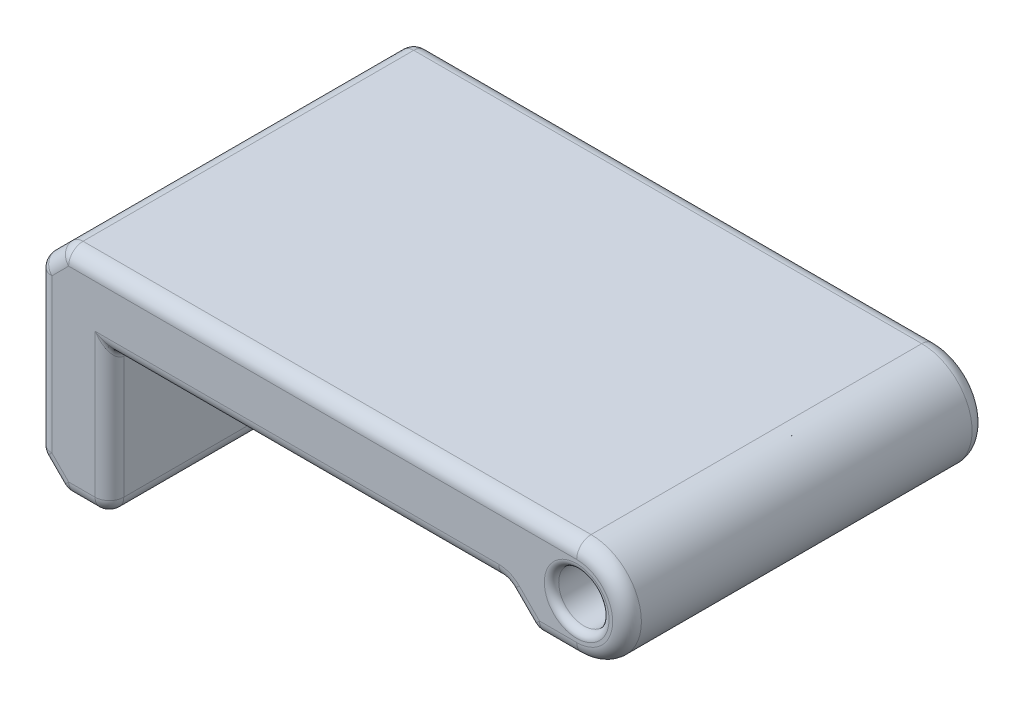
SolidWorks part; units mm, degrees
ref_plane "前视基准面" through (0, 0, 0) normal (0, 0, 1) x (1, 0, 0)
ref_plane "上视基准面" through (0, 0, 0) normal (0, 1, 0) x (1, 0, 0)
ref_plane "右视基准面" through (0, 0, 0) normal (1, 0, 0) x (0, 0, -1)
sketch "草图1" plane through (0, 0, 0) normal (0, 1, 0) x (1, 0, 0)
  line L0 (54.3761, 39.8273) -> (54.3761, 89.8273)
  line L1 (54.3761, 89.8273) -> (109.3761, 89.8273)
  line L2 (109.3761, 89.8273) -> (109.3761, 39.8273)
  line L3 (109.3761, 39.8273) -> (54.3761, 39.8273)
extrude "凸台-拉伸1" add sketch "草图1" along normal blind 10
sketch "草图2" plane through (0, 0, -39.8273) normal (0, 0, 1) x (1, 0, 0)
  line L2 (119.3761, -4) -> (113.3761, -4)
  line L7 (119.3761, 10) -> (109.3761, 10)
  line L8 (109.3761, 10) -> (109.3761, 0)
  line L9 (109.3761, 0) -> (113.3761, -4)
  arc A0 (119.3761, -4) -> (119.3761, 10) centre (119.3761, 3) ccw
  circle A1 centre (119.3761, 3) radius 3.5
extrude "凸台-拉伸2" add sketch "草图2" against normal up to surface (50 mm away) up to face at (81.8761, 5, -89.8273)
sketch "草图3" plane through (0, 0, -39.8273) normal (0, 0, 1) x (1, 0, 0)
  line L0 (54.3761, 0) -> (54.3761, -20)
  line L1 (54.3761, -20) -> (44.3761, -20)
  line L2 (44.3761, -20) -> (44.3761, 10)
  line L3 (44.3761, 10) -> (54.3761, 10)
  line L4 (54.3761, 10) -> (54.3761, 0)
extrude "凸台-拉伸3" add sketch "草图3" against normal up to surface (50 mm away) up to face at (96.2095, 2, -89.8273)
chamfer "倒角1" distance 3.5 angle 45 2 edges at (44.3761, -20, -64.8273) (44.3761, 10, -64.8273)
fillet "圆角1" radius 2 27 edges at (116.3761, -4, -89.8273) (126.3761, 3, -89.8273) (116.3761, -4, -39.8273) (126.3761, 3, -39.8273) (51.1261, -20, -39.8273) (54.3761, -20, -64.8273) (51.1261, -20, -89.8273) (111.3761, -2, -39.8273) (111.3761, -2, -89.8273) (83.6261, 10, -89.8273) (44.3761, -5, -89.8273) (54.3761, -10, -89.8273) (81.8761, 0, -89.8273) (81.8761, 0, -39.8273) (54.3761, -10, -39.8273) (44.3761, -5, -39.8273) (83.6261, 10, -39.8273) (109.3761, 0, -64.8273) (46.1261, -18.25, -89.8273) (46.1261, -18.25, -39.8273) (47.8761, -20, -64.8273) (44.3761, -16.5, -64.8273) (44.3761, 6.5, -64.8273) (47.8761, 10, -64.8273) (46.1261, 8.25, -89.8273) (46.1261, 8.25, -39.8273) (113.3761, -4, -64.8273)
fillet "圆角3" radius 1 3 edges at (53.7903, 0.5858, -89.2415) (53.7903, 0.5858, -40.4131) (54.3761, 0, -64.8273)
fillet "圆角4" radius 1 2 edges at (122.8761, 3, -39.8273) (122.8761, 3, -89.8273)
